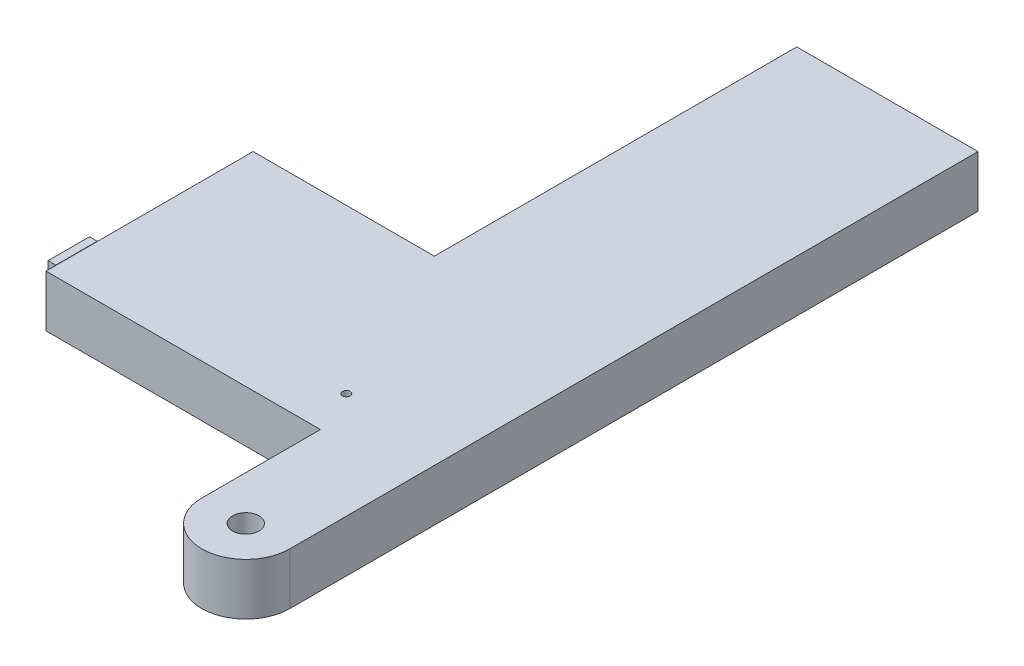
SolidWorks part; units mm, degrees
ref_plane "Front Plane" through (0, 0, 0) normal (0, 0, 1) x (1, 0, 0)
ref_plane "Top Plane" through (0, 0, 0) normal (0, 1, 0) x (1, 0, 0)
ref_plane "Right Plane" through (0, 0, 0) normal (1, 0, 0) x (0, 0, -1)
sketch "CornerrSketch1" plane through (0, 0, 0) normal (0, 1, 0) x (1, 0, 0)
  line L0 (0, 0) -> (0, 100)
  line L5 (0, 100) -> (50, 100)
  line L6 (50, 100) -> (50, 220)
  line L7 (140, 220) -> (50, 220)
  line L8 (106, -45.825) -> (106, 0)
  line L9 (0, 0) -> (106, 0)
  line L10 (140, 220) -> (140, -45.825)
  arc A0 (106, -45.825) -> (140, -45.825) centre (123, -45.825) ccw
  dimension "D5" = 34
  dimension "D4" = 100
  dimension "D3" = 90
  dimension "D1" = 220
  dimension "D2" = 45.825
  dimension "D6" = 140
extrude "CornerBoss-Extrude1" add sketch "CornerrSketch1" along normal blind 20
shell "Shell1" thickness 3 removed face at (74, 0, -66.4188)
sketch "PadSketch1" plane through (0, 17, 0) normal (0, -1, 0) x (1, 0, 0)
  line L1 (0, 0) -> (106, 0) construction
  line L2 (140, 45.825) -> (140, -220) construction
  circle A0 centre (99, -17) radius 5
  circle A1 centre (123, 45.825) radius 12
  dimension "D1" = 10
  dimension "D4" = 24
  dimension "D3" = 17
  dimension "D2" = 41
extrude "PadBoss-Extrude1" add sketch "PadSketch1" along normal blind 10
sketch "PutBackPartOfShellSketch1" plane through (0, 17, 0) normal (0, -1, 0) x (1, 0, 0)
  line L0 (3, -77) -> (73, -77)
  line L1 (73, -77) -> (73, -217)
  line L2 (73, -217) -> (53, -217)
  line L3 (53, -217) -> (53, -97)
  line L4 (53, -97) -> (3, -97)
  line L5 (3, -97) -> (3, -77)
  line L7 (50, -100) -> (0, -100) construction
  line L9 (53, -97) -> (3, -97) construction
  line L10 (3, -97) -> (3, -3) construction
  line L11 (3, -97) -> (3, -3) construction
  line L12 (137, -217) -> (53, -217) construction
  dimension "D1" = 23
extrude "PutBackPartOfShellBoss-Extrude1" add sketch "PutBackPartOfShellSketch1" along normal blind 17
sketch "TabHoleCutsSketch1" plane through (0, 0, 0) normal (0, -1, 0) x (1, 0, 0)
  line L1 (140, -220) -> (50, -220) construction
  line L2 (50, -220) -> (50, -100) construction
  line L3 (137, -3) -> (137, -217) construction
  line L4 (137, -217) -> (73, -217) construction
  line L5 (0, -100) -> (0, 0) construction
  line L6 (50, -100) -> (0, -100) construction
  circle A0 centre (20, -90) radius 1
  circle A1 centre (60, -90) radius 1
  circle A2 centre (60, -145) radius 1
  circle A3 centre (60, -200) radius 1
  dimension "D5" = 2
  dimension "D2" = 55
  dimension "D3" = 20
  dimension "D4" = 10
  dimension "D6" = 20
  dimension "D1" = 10
extrude "TabHoleCut-Extrude1" cut sketch "TabHoleCutsSketch1" against normal through all
sketch "StepperShaftCut-Sketch3" plane through (0, 7, 0) normal (0, -1, 0) x (1, 0, 0)
  circle A0 centre (123, 45.825) radius 5.1
  circle A1 centre (99, -17) radius 1.5
  dimension "D2" = 3
  dimension "D1" = 10.2
extrude "StepperShaftCut-Extrude1" cut sketch "StepperShaftCut-Sketch3" against normal through all
sketch "ThreadedNutMountHolesSketch5" plane through (0, 7, 0) normal (0, -1, 0) x (1, 0, 0)
  circle A0 centre (123, 53.825) radius 1
  circle A1 centre (131, 45.825) radius 1
  circle A2 centre (115, 45.825) radius 1
  circle A3 centre (123, 37.825) radius 1
  dimension "D3" = 2
  dimension "D1" = 8
  dimension "D2" = 16
  dimension "D4" = 8
  dimension "D5" = 16
extrude "ThreadedNutMountHolesCut-Extrude2" cut sketch "ThreadedNutMountHolesSketch5" against normal blind 10
sketch "TopPegHoleSketch4" plane through (0, 0, -220) normal (0, 0, -1) x (-1, 0, 0)
  line L1 (-130, 14) -> (-120, 14)
  line L2 (-130, 14) -> (-130, 0)
  line L3 (-130, 0) -> (-120, 0)
  line L4 (-120, 14) -> (-120, 0)
  line L5 (-140, 0) -> (-50, 0) construction
  line L6 (-140, 20) -> (-140, 0) construction
  dimension "D2" = 10
  dimension "D3" = 14
  dimension "D1" = 10
extrude "TopPegHoleCut-Extrude2" cut sketch "TopPegHoleSketch4" against normal blind 3
sketch "BLPegSketch5" plane through (0, 0, 0) normal (-1, 0, 0) x (0, 0, 1)
  line L1 (-19.9, 13.9) -> (-10.1, 13.9)
  line L2 (-19.9, 13.9) -> (-19.9, 0)
  line L3 (-19.9, 0) -> (-10.1, 0)
  line L4 (-10.1, 13.9) -> (-10.1, 0)
  line L5 (-100, 0) -> (0, 0) construction
  line L6 (0, 20) -> (0, 0) construction
  dimension "D2" = 13.9
  dimension "D3" = 9.8
  dimension "D1" = 10.1
extrude "BLPegBoss-Extrude3" add sketch "BLPegSketch5" along normal blind 3.1
sketch "BLPegCapSketch6" plane through (-3.1, 0, 0) normal (-1, 0, 0) x (0, 0, 1)
  line L0 (-19.9, 13.9) -> (-19.9, 0) construction
  line L1 (-22.9, 17) -> (-6.9, 17)
  line L2 (-22.9, 17) -> (-22.9, 0)
  line L3 (-22.9, 0) -> (-6.9, 0)
  line L4 (-6.9, 17) -> (-6.9, 0)
  line L8 (-19.9, 0) -> (-10.1, 0) construction
  dimension "D1" = 16
  dimension "D3" = 17
  dimension "D2" = 3
extrude "BLPegCapBoss-Extrude4" add sketch "BLPegCapSketch6" along normal blind 3
chamfer "OverlapChamfer1" distance 20 distance2 20 2 edges at (50, 20, -160) (25, 20, -100)
equation "\"BedThickness\"= 20mm"
equation "\"BedToBuildPlateStandoffHolesDistanceFromLeftOrRight\"= \"BuildPlateStandoffHolesDistanceFromLeftOrRight\" + \"BedIncreasedByWidth\" / 2'Equals 17"
equation "\"BedToBuildPlateStandoffHoleSize\"= 3mm"
equation "\"BedLLongSide\"= \"BedThirdSize\" * 3'Equals 210"
equation "\"BedLShortSide\"= \"BedThirdSize\" * 2'Equals 140"
equation "\"BedLWidth\"= \"BedThirdSize\" + \"BedOverlap\"'Equals 90"
equation "\"D4@CornerrSketch1\"=\"BedLWidth\" + \"BedIncreasedByWidth\"/2"
equation "\"BedIncreasedByWidth\"= 20mm"
equation "\"BedIncreasedByLength\"= 0mm"
equation "\"BedThirdSize\"= 70mm"
equation "\"BedOverlap\"= 20mm"
equation "\"D3@TabHoleCutsSketch1\" = \"BedOverlap\""
equation "\"D4@TabHoleCutsSketch1\" = \"BedOverlap\" / 2"
equation "\"D6@TabHoleCutsSketch1\" = \"BedOverlap\""
equation "\"StandardWallThickness\"= 3mm"
equation "\"D2@TopPegHoleSketch4\"=\"BedTopPegHoleWidth\""
equation "\"D3@TopPegHoleSketch4\"=\"BedTopPegHoleHeight\""
equation "\"D1@TopPegHoleCut-Extrude2\" = \"StandardWallThickness\""
equation "\"D3@BLPegSketch5\"=\"BedTopPegWidth\""
equation "\"D1@BLPegBoss-Extrude3\"=\"BedTopPegBoss\""
equation "\"D2@BLPegSketch5\"=\"BedTopPegHeight\""
equation "\"D2@BLPegCapSketch6\"=\"StandardWallThickness\""
equation "\"D3@BLPegCapSketch6\"=\"BedTopPegCapHeight\""
equation "\"D1@BLPegCapBoss-Extrude4\" = \"StandardWallThickness\""
equation "\"D3@CornerrSketch1\"=\"BedLWidth\" "
equation "\"D1@PadSketch1\" = \"BedToBuildPlateStandoffPadSize\""
equation "\"D1@PadBoss-Extrude1\"=\"LeadScrewNutPadDepth\""
equation "\"BedToBuildPlateStandoffPadSize\"= 10mm"
equation "\"BedToBuildPlateStandoffHolesDistanceFromBack\"= \"BuildPlateStandoffHolesDistanceFromBack\" + \"BedIncreasedByLength\" / 2'Equals 41"
equation "\"BuildPlateStandoffHolesDistanceFromLeftOrRight\"= 7mm"
equation "\"BuildPlateStandoffHolesDistanceFromBack\"= 41mm"
equation "\"DistanceFromBedSideToStepperHole\"= ( \"DistanceBetweenLeftToRightStepperHoles\" - \"BedWidth\" ) / 2'Equals 45.825"
equation "\"DistanceBetweenLeftToRightStepperHoles\"= \"FrontBackRailLength\" - \"StepperMountingHoleOffsetFromLeftOrRightSide\" * 2 - \"StepperMountingHoleDistance\"'Equals 461.65"
equation "\"FrontBackRailLength\"= 510mm"
equation "\"StepperMountingHoleOffsetFromLeftOrRightSide\"= \"StepperMountingHoleOffsetFromItsSide\" + \"RailThickness\""
equation "\"StepperMountingHoleDistance\"= 31mm'Spec"
equation "\"StepperMountingHoleOffsetFromItsSide\"= 5.5mm'Spec"
equation "\"RailThickness\"= .125in'Spec"
equation "\"BedWidth\"= \"BedInnerSquareWidth\" + \"BedLWidth\" * 2 - \"BedOverlap\" * 2 + \"BedIncreasedByWidth\"'Equals 370"
equation "\"BedInnerSquareWidth\"= \"BedThirdSize\" * 3'Equals 210"
equation "\"D1@CornerrSketch1\"=\"BedLLongSide\"  + \"BedIncreasedByWidth\"/2"
equation "\"D2@CornerrSketch1\"=\"DistanceFromBedSideToStepperHole\""
equation "\"D3@PadSketch1\"=\"BedToBuildPlateStandoffHolesDistanceFromLeftOrRight\""
equation "\"D2@PadSketch1\"=\"BedToBuildPlateStandoffHolesDistanceFromBack\""
equation "\"D1@TopPegHoleSketch4\"=\"BedTopPegOffsetFromSide\""
equation "\"D1@BLPegSketch5\"=\"BedTopPegOffsetFromSide\" + .1mm"
equation "\"D6@CornerrSketch1\"=\"BedLShortSide\" + \"BedIncreasedByLength\"/2"
equation "\"LeadScrewNutPadSize\"= \"LeadScrewNutMountingHoleFlangeDiameter\" + 2mm'Equals 24"
equation "\"D4@PadSketch1\"=\"LeadScrewNutPadSize\""
equation "\"D1@StepperShaftCut-Sketch3\"=\"LeadScrewNutInnerShaftFlangeDiameter\""
equation "\"D2@StepperShaftCut-Sketch3\" = \"BedToBuildPlateStandoffHoleSize\""
equation "\"LeadScrewNutInnerShaftFlangeDiameter\"= 10.2mm'Spec"
equation "\"LeadScrewNutMountHoleDiameter\"= 2mm'Spec is 4.1 but smaller for tapping"
equation "\"LeadScrewNutMountingHoleFlangeDiameter\"= 22mm'Spec"
equation "\"LeadScrewNutMountingHoleDistance\"= 16mm'Spec"
equation "\"D1@ThreadedNutMountHolesSketch5\"=\"LeadScrewNutMountingHoleDistance\"/2"
equation "\"D2@ThreadedNutMountHolesSketch5\"=\"LeadScrewNutMountingHoleDistance\""
equation "\"D4@ThreadedNutMountHolesSketch5\"=\"LeadScrewNutMountingHoleDistance\"/2"
equation "\"D5@ThreadedNutMountHolesSketch5\"=\"LeadScrewNutMountingHoleDistance\""
equation "\"D3@ThreadedNutMountHolesSketch5\"=\"LeadScrewNutMountHoleDiameter\""
equation "\"LeadScrewNutPadDepth\"= \"BedThickness\" / 2'Equals 10"
equation "\"D1@ThreadedNutMountHolesCut-Extrude2\"= \"LeadScrewNutPadDepth\""
equation "\"BedTopPegHoleWidth\"= 10mm"
equation "\"BedTopPegHoleHeight\"= \"BedThickness\"- \"StandardWallThickness\"* 2' Equals 14"
equation "\"BedTopPegWidth\"= \"BedTopPegHoleWidth\"- .1mm* 2'For easier assembly"
equation "\"BedTopPegHeight\"= \"BedTopPegHoleHeight\"- .1mm'For easier assembly"
equation "\"BedTopPegOffsetFromSide\"= 10mm"
equation "\"BedTopPegBoss\"= \"StandardWallThickness\"+ .1mm'For easier assembly"
equation "\"BedTopPegCapHeight\"= \"BedThickness\"- \"StandardWallThickness\"'Equals 17"
equation "\"BedTopPegCapWidth\"= \"BedThickness\"/2 + \"StandardWallThickness\"*2'Equals 16"
equation "\"D1@PutBackPartOfShellSketch1\"=\"BedOverlap\" + \"StandardWallThickness\""
equation "\"D1@PutBackPartOfShellBoss-Extrude1\"=\"BedThickness\"- \"StandardWallThickness\""
equation "\"D3@OverlapChamfer1\"=\"BedOverlap\""
equation "\"D1@OverlapChamfer1\"=\"BedThickness\""
equation "\"D1@BLPegCapSketch6\"=\"BedTopPegCapWidth\""
